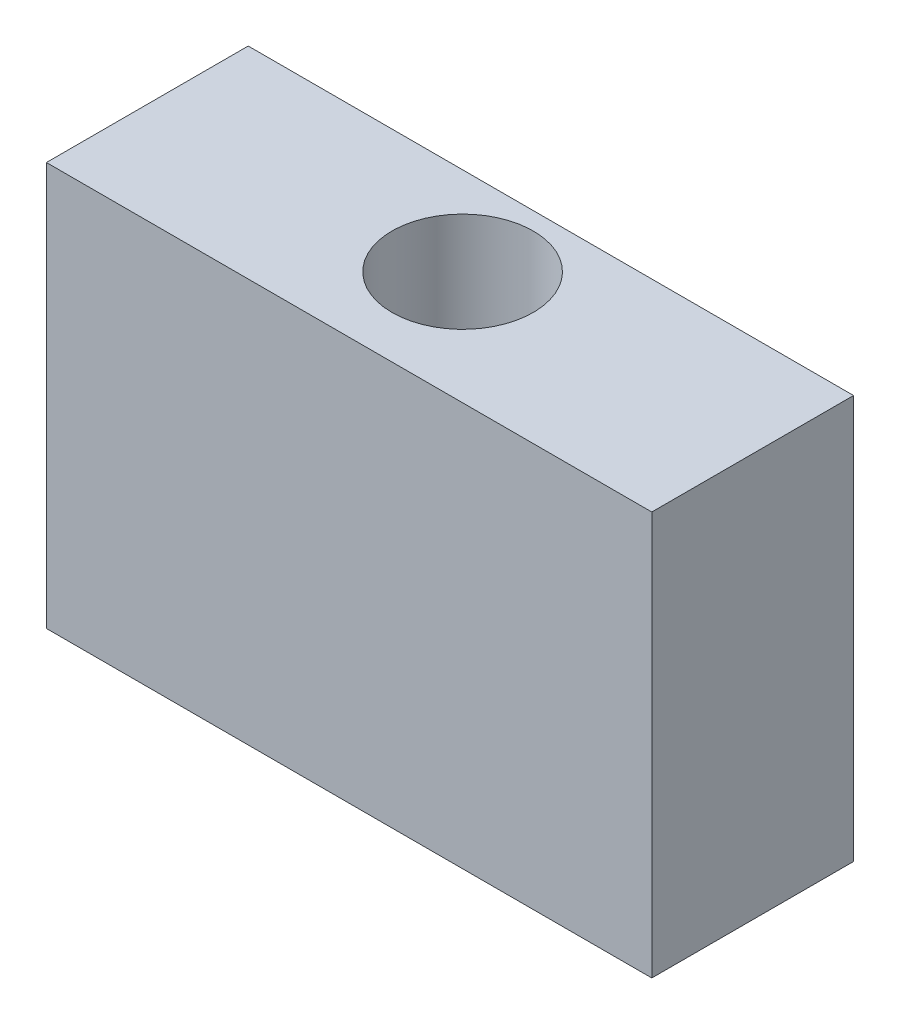
SolidWorks part; units mm, degrees
material "Polyethylene Cross-Linked"
ref_plane "Front Plane" through (0, 0, 0) normal (0, 0, 1) x (1, 0, 0)
ref_plane "Top Plane" through (0, 0, 0) normal (0, 1, 0) x (1, 0, 0)
ref_plane "Right Plane" through (0, 0, 0) normal (1, 0, 0) x (0, 0, -1)
sketch "Sketch1" plane through (0, 0, 0) normal (0, 1, 0) x (1, 0, 0)
  line L1 (0, 0) -> (38.1, 0)
  line L2 (0, 0) -> (0, 12.7)
  line L3 (0, 12.7) -> (38.1, 12.7)
  line L4 (38.1, 0) -> (38.1, 12.7)
  circle A0 centre (19.05, 7.1437) radius 4.445
extrude "Boss-Extrude1" add sketch "Sketch1" along normal blind 25.4
